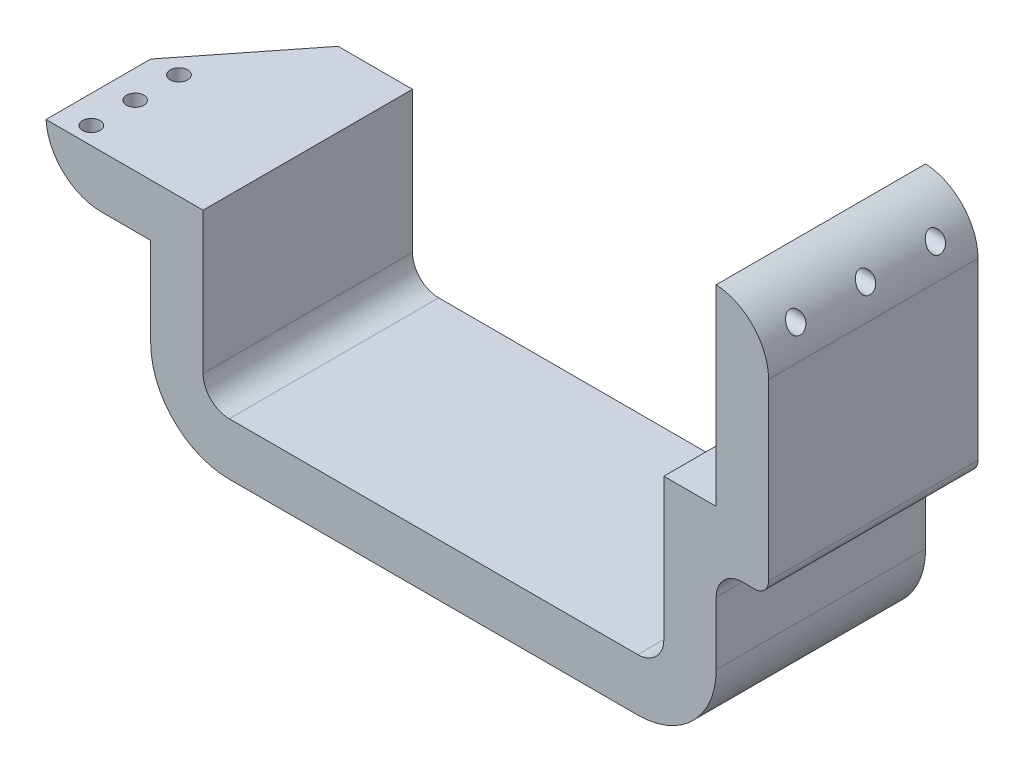
SolidWorks part; units mm, degrees
ref_plane "Front Plane" through (0, 0, 0) normal (0, 0, 1) x (1, 0, 0)
ref_plane "Top Plane" through (0, 0, 0) normal (0, 1, 0) x (1, 0, 0)
ref_plane "Right Plane" through (0, 0, 0) normal (1, 0, 0) x (0, 0, -1)
sketch "Sketch1" plane through (0, 0, 0) normal (0, 0, 1) x (1, 0, 0)
  line L0 (-40.64, 12.7) -> (-50.165, 12.7) construction
  line L1 (-38.1, -12.7) -> (38.1, -12.7) construction
  line L2 (-38.1, -12.7) -> (-38.1, 12.7) construction
  line L3 (-38.1, 12.7) -> (38.1, 12.7) construction
  line L4 (38.1, -12.7) -> (38.1, 12.7) construction
  line L5 (-38.1, -12.7) -> (38.1, 12.7) construction
  line L6 (-38.1, 12.7) -> (38.1, -12.7) construction
  line L7 (-40.64, 12.7) -> (-40.64, -13.0175) construction
  line L8 (43.18, 12.7) -> (52.705, 12.7) construction
  line L9 (52.705, 12.7) -> (52.705, 22.225) construction
  line L10 (52.705, 22.225) -> (62.23, 22.225) construction
  line L11 (-35.8775, -17.78) -> (38.4175, -17.78) construction
  line L12 (43.18, -13.0175) -> (43.18, 12.7) construction
  line L13 (-50.165, 12.7) -> (-50.165, -13.0175) construction
  line L14 (-35.8775, -27.305) -> (38.4175, -27.305)
  line L15 (52.705, -13.0175) -> (52.705, -1.5875) construction
  line L16 (57.4675, 3.175) -> (62.23, 3.175) construction
  line L17 (62.23, 3.175) -> (62.23, 22.225) construction
  line L18 (52.705, -13.0175) -> (52.705, 3.175) construction
  line L19 (52.705, 3.175) -> (62.23, 3.175) construction
  line L20 (-50.165, -13.0175) -> (-50.165, 12.7) construction
  line L21 (-50.165, 12.7) -> (-40.64, 12.7)
  line L22 (-40.64, 12.7) -> (-40.64, -13.0175)
  line L23 (-35.8775, -17.78) -> (38.4175, -17.78)
  line L24 (43.18, -13.0175) -> (43.18, 12.7)
  line L25 (43.18, 12.7) -> (52.705, 12.7)
  line L29 (57.4675, 3.175) -> (62.23, 3.175)
  line L30 (52.705, -1.5875) -> (52.705, -13.0175)
  line L34 (-50.165, 3.175) -> (-50.165, -13.0175)
  line L35 (-50.165, 12.7) -> (-59.69, 12.7)
  line L36 (-59.69, 12.7) -> (-69.215, 12.7)
  line L37 (-69.215, 12.7) -> (-69.215, 3.175)
  line L38 (-69.215, 3.175) -> (-50.165, 3.175)
  line L39 (52.705, 12.7) -> (52.705, 47.625)
  line L40 (52.705, 47.625) -> (62.23, 47.625)
  line L41 (62.23, 47.625) -> (62.23, 3.175)
  arc A0 (-40.64, -13.0175) -> (-35.8775, -17.78) centre (-35.8775, -13.0175) ccw construction
  arc A1 (38.4175, -17.78) -> (43.18, -13.0175) centre (38.4175, -13.0175) ccw construction
  arc A2 (-50.165, -13.0175) -> (-35.8775, -27.305) centre (-35.8775, -13.0175) ccw
  arc A3 (38.4175, -27.305) -> (52.705, -13.0175) centre (38.4175, -13.0175) ccw
  arc A4 (52.705, -1.5875) -> (57.4675, 3.175) centre (57.4675, -1.5875) cw construction
  arc A5 (-40.64, -13.0175) -> (-35.8775, -17.78) centre (-35.8775, -13.0175) ccw
  arc A6 (38.4175, -17.78) -> (43.18, -13.0175) centre (38.4175, -13.0175) ccw
  arc A7 (52.705, -1.5875) -> (57.4675, 3.175) centre (57.4675, -1.5875) cw
  point P0 (0, 0)
  dimension "D7" = 4.7625
  dimension "D9" = 25.4
  dimension "D1" = 76.2
  dimension "D2" = 25.4
  dimension "D3" = 9.525
  dimension "D4" = 2.54
  dimension "D5" = 5.08
  dimension "D6" = 5.08
  dimension "D8" = 9.525
extrude "Boss-Extrude1" add sketch "Sketch1" along normal blind 38.1
fillet "Fillet1" radius 2.54 1 edges at (62.23, 3.175, 19.05)
fillet "Fillet2" radius 10.16 2 edges at (-69.215, 3.175, 19.05) (62.23, 47.625, 19.05)
sketch "Sketch2" plane through (0, 3.175, 0) normal (0, -1, 0) x (1, 0, 0)
  line L0 (-69.215, 19.05) -> (-50.165, 43.18) construction
  line L1 (-50.165, 43.18) -> (-50.165, 19.05) construction
  line L2 (-50.165, 38.1) -> (-50.165, 0) construction
  line L3 (-50.165, 19.05) -> (-69.215, 19.05) construction
  line L4 (-35.8775, 0) -> (38.4175, 0) construction
  line L5 (-69.215, 19.05) -> (-69.215, 43.18) construction
  line L6 (-69.215, 43.18) -> (-50.165, 43.18) construction
  line L7 (-69.215, -5.08) -> (-50.165, -5.08)
  line L8 (-50.165, -5.08) -> (-69.215, 19.05)
  line L9 (-69.215, 38.1) -> (-69.215, 0) construction
  line L10 (-69.215, 19.05) -> (-69.215, -5.08)
  line L11 (-69.215, 19.05) -> (-50.165, 19.05) construction
  line L12 (-50.165, 38.1) -> (-50.165, 0) construction
  line L13 (-59.0749, 38.1) -> (-69.215, 38.1) construction
  dimension "D1" = 19.05
  dimension "D2" = 24.13
  dimension "D3" = 19.05
  dimension "D4" = 19.05
  dimension "D5" = 24.13
  dimension "D6" = 19.05
extrude "Cut-Extrude2" cut sketch "Sketch2" against normal through all
sketch "Sketch3" plane through (62.23, 0, 0) normal (1, 0, 0) x (0, 0, -1)
  line L0 (-38.1, 42.5549) -> (0, 42.5549) construction
  line L1 (-38.1, 47.625) -> (-38.1, 37.4849) construction
  line L2 (0, 37.4849) -> (0, 47.625) construction
  circle A0 centre (-6.35, 42.5549) radius 1.5875
  circle A1 centre (-19.05, 42.5549) radius 1.5875
  circle A2 centre (-31.75, 42.5549) radius 1.5875
  dimension "D1" = 3.175
  dimension "D2" = 6.35
  dimension "D4" = 6.35
  dimension "D3" = 3
extrude "Cut-Extrude3" cut sketch "Sketch3" against normal through all
sketch "Sketch4" plane through (0, 3.175, 0) normal (0, -1, 0) x (1, 0, 0)
  line L0 (-64.1449, 38.1) -> (-64.1449, 12.6279) construction
  line L1 (-59.0749, 38.1) -> (-69.215, 38.1) construction
  line L2 (-69.215, 19.05) -> (-59.0749, 6.2058) construction
  circle A0 centre (-64.1449, 34.925) radius 1.5875
  circle A1 centre (-64.1449, 26.9515) radius 1.5875
  circle A2 centre (-64.1449, 18.9779) radius 1.5875
  dimension "D1" = 3.175
  dimension "D2" = 3.175
  dimension "D4" = 6.35
  dimension "D3" = 3
extrude "Cut-Extrude4" cut sketch "Sketch4" against normal through all
